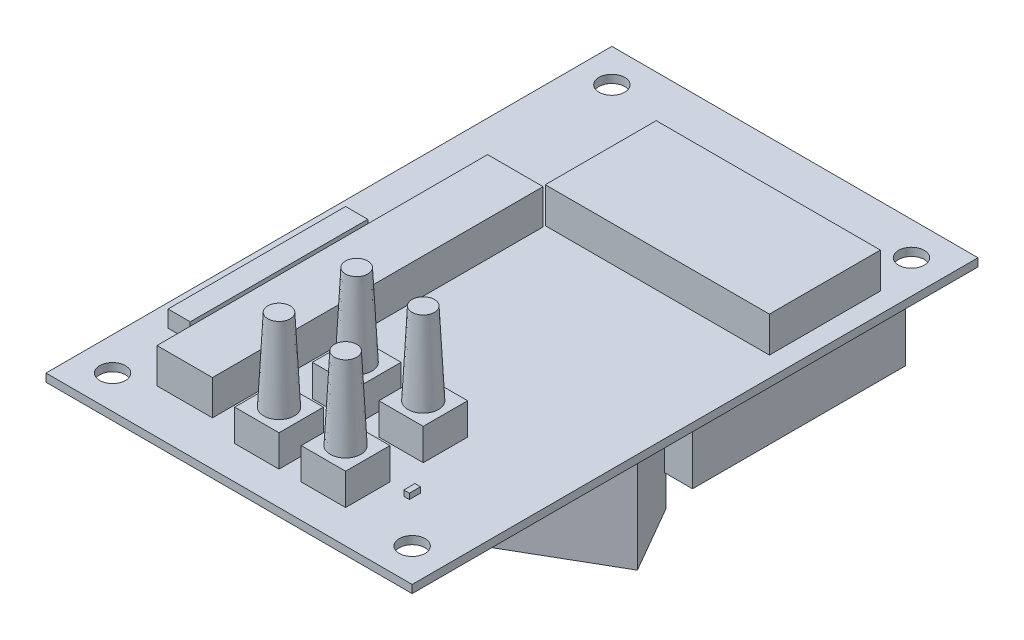
SolidWorks part; units mm, degrees
ref_plane "Front Plane" through (0, 0, 0) normal (0, 0, 1) x (1, 0, 0)
ref_plane "Top Plane" through (0, 0, 0) normal (0, 1, 0) x (1, 0, 0)
ref_plane "Right Plane" through (0, 0, 0) normal (1, 0, 0) x (0, 0, -1)
sketch "Sketch1" plane through (0, 0, 0) normal (0, 1, 0) x (1, 0, 0)
  line L1 (0, 0) -> (41.91, 0)
  line L2 (0, 0) -> (0, 64.77)
  line L3 (0, 64.77) -> (41.91, 64.77)
  line L4 (41.91, 0) -> (41.91, 64.77)
  dimension "D1" = 41.91
  dimension "D2" = 64.77
extrude "Boss-Extrude1" add sketch "Sketch1" along normal blind 0.9144
sketch "ButtonBase" plane through (0, 0.9144, 0) normal (0, 1, 0) x (1, 0, 0)
  line L0 (0, 64.77) -> (0, 0) construction
  line L1 (17.78, 12.7) -> (22.86, 12.7)
  line L2 (17.78, 12.7) -> (17.78, 17.78)
  line L3 (17.78, 17.78) -> (22.86, 17.78)
  line L4 (22.86, 12.7) -> (22.86, 17.78)
  line L5 (17.78, 12.7) -> (22.86, 17.78) construction
  line L6 (17.78, 17.78) -> (22.86, 12.7) construction
  line L7 (0, 0) -> (41.91, 0) construction
  line L8 (30.48, 12.7) -> (30.48, 17.78)
  line L9 (25.4, 17.78) -> (30.48, 12.7) construction
  line L10 (25.4, 17.78) -> (30.48, 17.78)
  line L11 (25.4, 12.7) -> (25.4, 17.78)
  line L12 (25.4, 12.7) -> (30.48, 17.78) construction
  line L13 (25.4, 12.7) -> (30.48, 12.7)
  line L14 (30.48, 3.81) -> (30.48, 8.89)
  line L15 (25.4, 8.89) -> (30.48, 3.81) construction
  line L16 (25.4, 8.89) -> (30.48, 8.89)
  line L17 (25.4, 3.81) -> (25.4, 8.89)
  line L18 (25.4, 3.81) -> (30.48, 8.89) construction
  line L19 (25.4, 3.81) -> (30.48, 3.81)
  line L20 (22.86, 3.81) -> (22.86, 8.89)
  line L21 (17.78, 8.89) -> (22.86, 3.81) construction
  line L22 (17.78, 8.89) -> (22.86, 8.89)
  line L23 (17.78, 3.81) -> (17.78, 8.89)
  line L24 (17.78, 3.81) -> (22.86, 8.89) construction
  line L25 (17.78, 3.81) -> (22.86, 3.81)
  point P0 (20.32, 15.24)
  dimension "D1" = 20.32
  dimension "D2" = 15.24
  dimension "D3" = 5.08
  dimension "ButtonSepX" = 7.62
  dimension "ButtonSepY" = 8.89
  dimension "D4" = 2
  dimension "D5" = 2
extrude "Boss-Extrude2" add sketch "ButtonBase" along normal blind 3.6068
sketch "Sketch4" plane through (0, 0.9144, 0) normal (0, 1, 0) x (1, 0, 0)
  line L0 (0, 0) -> (41.91, 0) construction
  line L1 (13.97, 43.18) -> (39.624, 43.18)
  line L2 (13.97, 43.18) -> (13.97, 55.88)
  line L3 (13.97, 55.88) -> (39.624, 55.88)
  line L4 (39.624, 43.18) -> (39.624, 55.88)
  line L5 (0, 64.77) -> (0, 0) construction
  dimension "D1" = 43.18
  dimension "D2" = 13.97
  dimension "D3" = 12.7
  dimension "D4" = 25.654
extrude "Boss-Extrude3" add sketch "Sketch4" along normal blind 4.064
hole_wizard "#32 (0.116) Diameter Hole1" positions "Sketch7" profile "Sketch6" hole size "#32" standard "ANSI Inch"
sketch "Sketch7" plane through (0, 0.9144, 0) normal (0, 1, 0) x (1, 0, 0)
  line L0 (0, 0) -> (41.91, 0) construction
  line L1 (0, 64.77) -> (0, 0) construction
  point P0 (3.81, 60.96)
  point P2 (38.1, 60.96)
  point P4 (38.1, 3.81)
  point P6 (3.81, 3.81)
  dimension "D1" = 3.81
  dimension "D2" = 3.81
  dimension "D3" = 38.1
  dimension "D4" = 3.81
  dimension "D5" = 60.96
sketch "Sketch6" plane through (3.81, 0.9144, -60.96) normal (1, 0, 0) x (0, 0, 1)
  line L0 (0, 0) -> (0, 26.2852)
  line L1 (0, 26.2852) -> (1.4732, 25.4)
  line L2 (1.4732, 25.4) -> (1.4732, 0)
  line L5 (1.4732, 0) -> (0, 0)
  line L10 (0, 26.2852) -> (-1.4732, 25.4) construction
  line L11 (0, -6.35) -> (0, 107.95) construction
  dimension "Hole Dia." = 2.9464
  dimension "Hole Depth" = 25.4
  dimension "Drill Angle" = 118
sketch "Sketch8" plane through (0, 0.9144, 0) normal (0, 1, 0) x (1, 0, 0)
  line L0 (0, 0) -> (41.91, 0) construction
  line L1 (32.7025, 8.255) -> (33.3375, 8.255)
  line L2 (32.7025, 8.255) -> (32.7025, 9.525)
  line L3 (32.7025, 9.525) -> (33.3375, 9.525)
  line L4 (33.3375, 8.255) -> (33.3375, 9.525)
  line L5 (32.7025, 8.255) -> (33.3375, 9.525) construction
  line L6 (32.7025, 9.525) -> (33.3375, 8.255) construction
  line L8 (0, 64.77) -> (0, 0) construction
  point P0 (33.02, 8.89)
  dimension "D1" = 8.89
  dimension "D2" = 33.02
  dimension "D3" = 0.635
  dimension "D4" = 1.27
extrude "Boss-Extrude4" add sketch "Sketch8" along normal blind 0.635
sketch "Sketch10" plane through (0, 0, 0) normal (0, -1, 0) x (1, 0, 0)
  line L0 (41.4782, -26.2182) -> (28.9179, -18.9665)
  line L1 (41.4782, -26.2182) -> (36.9824, -34.0052)
  line L2 (28.9179, -18.9665) -> (24.4221, -26.7535)
  line L3 (36.9824, -34.0052) -> (24.4221, -26.7535)
  line L4 (41.4782, -26.2182) -> (24.4221, -26.7535) construction
  line L5 (28.9179, -18.9665) -> (36.9824, -34.0052) construction
  line L6 (41.91, 0) -> (41.91, -64.77) construction
  line L7 (0, -64.77) -> (0, 0) construction
  line L9 (0, 0) -> (41.91, 0) construction
  point P0 (26.67, -22.86)
  point P1 (32.9502, -26.4859)
  dimension "D1" = 26.67
  dimension "D2" = 22.86
  dimension "D3" = 8.9916
  dimension "D4" = 14.5034
  dimension "D5" = 60
extrude "Boss-Extrude5" add sketch "Sketch10" along normal blind 10.9982
sketch "Sketch11" plane through (0, 0, 0) normal (0, -1, 0) x (1, 0, 0)
  line L0 (19.3929, -57.912) -> (12.8651, -50.3174)
  line L1 (40.4749, -57.912) -> (40.4749, -33.528)
  line L2 (40.4749, -57.912) -> (19.3929, -57.912)
  line L3 (19.3929, -57.912) -> (19.3929, -33.528) construction
  line L4 (40.4749, -33.528) -> (19.3929, -33.528)
  line L5 (12.8651, -50.3174) -> (12.8651, -41.1226)
  line L6 (12.8651, -41.1226) -> (19.3929, -33.528)
  line L7 (12.8651, -45.72) -> (40.4749, -45.72) construction
  line L10 (0, -64.77) -> (0, 0) construction
  line L11 (0, 0) -> (41.91, 0) construction
  line L12 (26.67, -45.72) -> (26.67, -33.528) construction
  line L13 (26.67, -33.528) -> (26.67, -57.912) construction
  point P8 (26.67, -45.72)
  point P16 (0, 0)
  dimension "D1" = 24.384
  dimension "D2" = 6.5278
  dimension "D3" = 27.6098
  dimension "D4" = 7.5946
  dimension "D5" = 26.67
  dimension "D6" = 45.72
extrude "Boss-Extrude6" add sketch "Sketch11" along normal blind 7.09
sketch "Sketch12" plane through (0, 4.5212, 0) normal (0, 1, 0) x (1, 0, 0)
  line L0 (20.32, 17.78) -> (20.32, 12.7) construction
  line L1 (22.86, 17.78) -> (17.78, 17.78) construction
  line L2 (17.78, 12.7) -> (22.86, 12.7) construction
  line L3 (20.32, 12.7) -> (20.32, 3.81) construction
  line L4 (17.78, 3.81) -> (22.86, 3.81) construction
  line L5 (17.78, 15.24) -> (30.48, 15.24) construction
  line L6 (17.78, 17.78) -> (17.78, 12.7) construction
  line L7 (30.48, 12.7) -> (30.48, 17.78) construction
  circle A0 centre (20.32, 15.24) radius 1.7526
  circle A1 centre (27.94, 15.24) radius 1.7526
  circle A2 centre (27.94, 6.35) radius 1.7526
  circle A3 centre (20.32, 6.35) radius 1.7526
  point P15 (20.32, 15.24)
  point P17 (27.94, 15.24)
  point P19 (27.94, 6.35)
  point P20 (20.32, 6.35)
  dimension "D5" = 3.5052
  dimension "D3" = 7.62
  dimension "D4" = 8.89
  dimension "D1" = 2
  dimension "D2" = 2
  dimension "D6" = 2
  dimension "D7" = 2
extrude "Boss-Extrude7" add sketch "Sketch12" along normal blind 9.398
draft "Draft5" type of draft neutral plane draft angle 2.87 faces to draft 4 face at (27.94, 13.9192, -4.5974) face at (27.94, 13.9192, -13.4874) face at (20.32, 13.9192, -13.4874) face at (20.32, 13.9192, -4.5974) neutral plane through (0, 4.5212, 0) neutral plane normal (0, 1, 0) parameters "D1"=2.87
sketch "Sketch13" plane through (0, 0.9144, 0) normal (0, 1, 0) x (1, 0, 0)
  line L0 (0, 64.77) -> (0, 0) construction
  line L1 (7.62, 5.08) -> (13.97, 5.08)
  line L2 (7.62, 5.08) -> (7.62, 42.926)
  line L3 (7.62, 42.926) -> (13.97, 42.926)
  line L4 (13.97, 5.08) -> (13.97, 42.926)
  line L5 (0, 0) -> (41.91, 0) construction
  dimension "D1" = 7.62
  dimension "D2" = 5.08
  dimension "D3" = 6.35
  dimension "D4" = 37.846
extrude "Boss-Extrude8" add sketch "Sketch13" along normal blind 4
sketch "Sketch15" plane through (0, 0, 0) normal (0, -1, 0) x (-1, 0, 0)
  line L0 (0, 64.77) -> (0, 0) construction
  line L1 (-2.54, 11.43) -> (-5.08, 11.43)
  line L2 (-2.54, 11.43) -> (-2.54, 31.75)
  line L3 (-2.54, 31.75) -> (-5.08, 31.75)
  line L4 (-5.08, 11.43) -> (-5.08, 31.75)
  line L5 (0, 0) -> (-41.91, 0) construction
  dimension "D1" = 2.54
  dimension "D2" = 20.32
  dimension "D3" = 2.54
  dimension "D4" = 11.43
extrude "Boss-Extrude9" add sketch "Sketch15" along normal blind 8.89 and the other way blind 2.8194
